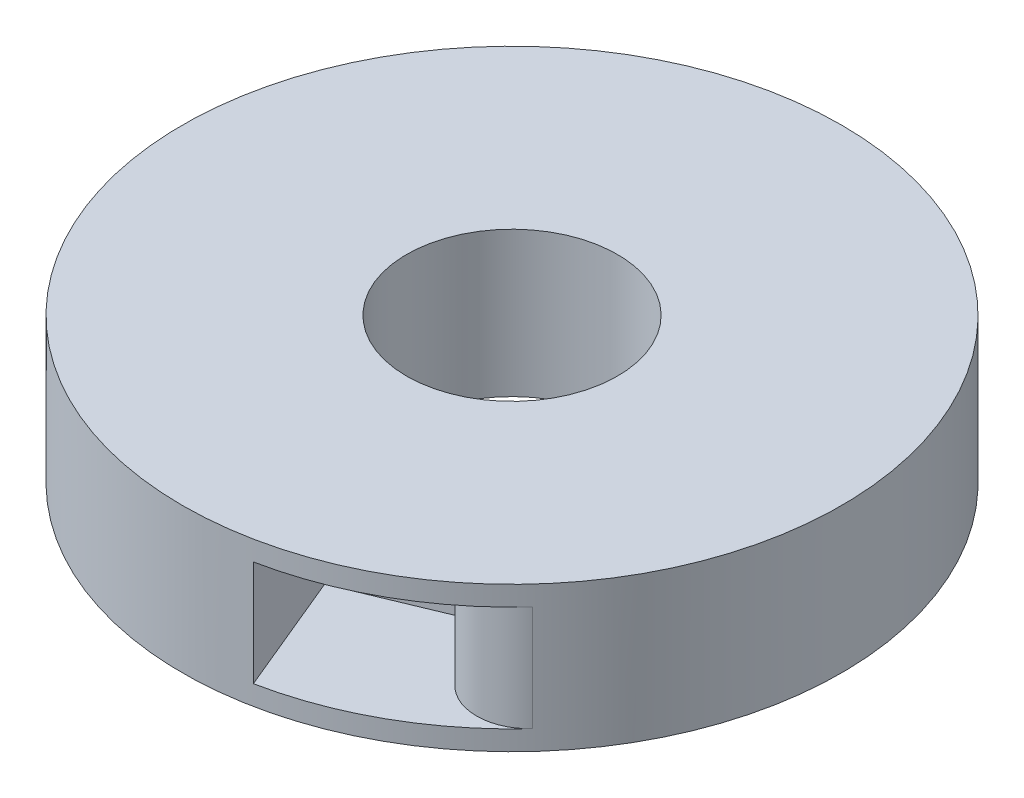
SolidWorks part; units mm, degrees
ref_plane "Front Plane" through (0, 0, 0) normal (0, 0, 1) x (1, 0, 0)
ref_plane "Top Plane" through (0, 0, 0) normal (0, 1, 0) x (1, 0, 0)
ref_plane "Right Plane" through (0, 0, 0) normal (1, 0, 0) x (0, 0, -1)
sketch "Sketch1" plane through (0, 0, 0) normal (0, 1, 0) x (1, 0, 0)
  line L0 (4.8944, -24.5162) -> (1.0612, -15.2801)
  line L1 (-4.8944, 24.5162) -> (-1.0612, 15.2801)
  line L2 (-1.0612, 15.2801) -> (-10.0702, 11.5412)
  line L3 (-10.0702, 11.5412) -> (-13.9034, 20.7773)
  line L4 (1.0612, -15.2801) -> (10.0702, -11.5412)
  line L5 (10.0702, -11.5412) -> (13.9034, -20.7773)
  circle A0 centre (0, 0) radius 25
  point P14 (-0.6216, 3.7007)
  point P15 (0, 0)
  dimension "D3" = 50
  dimension "D1" = 10
  dimension "D2" = 90
  dimension "D4" = 10
  dimension "D5" = 90
  dimension "D7" = 9.754
  dimension "D6" = 2
extrude "Boss-Extrude1" add sketch "Sketch1" along normal blind 8 contours L5 A0 L1 L2 L3 L0 L4 region at (0, 0, 0)
sketch "Sketch2" plane through (0, 8, 0) normal (0, 1, 0) x (1, 0, 0)
  circle A0 centre (0, 0) radius 25
extrude "Boss-Extrude2" add sketch "Sketch2" along normal blind 1.5
sketch "Sketch3" plane through (0, 0, 0) normal (0, -1, 0) x (-1, 0, 0)
  circle A0 centre (0, 0) radius 25
extrude "Boss-Extrude3" add sketch "Sketch3" along normal blind 1.5
sketch "Sketch4" plane through (0, 9.5, 0) normal (0, 1, 0) x (1, 0, 0)
  circle A0 centre (0, 0) radius 8
  dimension "D1" = 16
extrude "Cut-Extrude1" cut sketch "Sketch4" against normal through all
fillet "Fillet1" radius 4 2 edges at (-13.9034, 4, -20.7773) (13.9034, 4, 20.7773)
